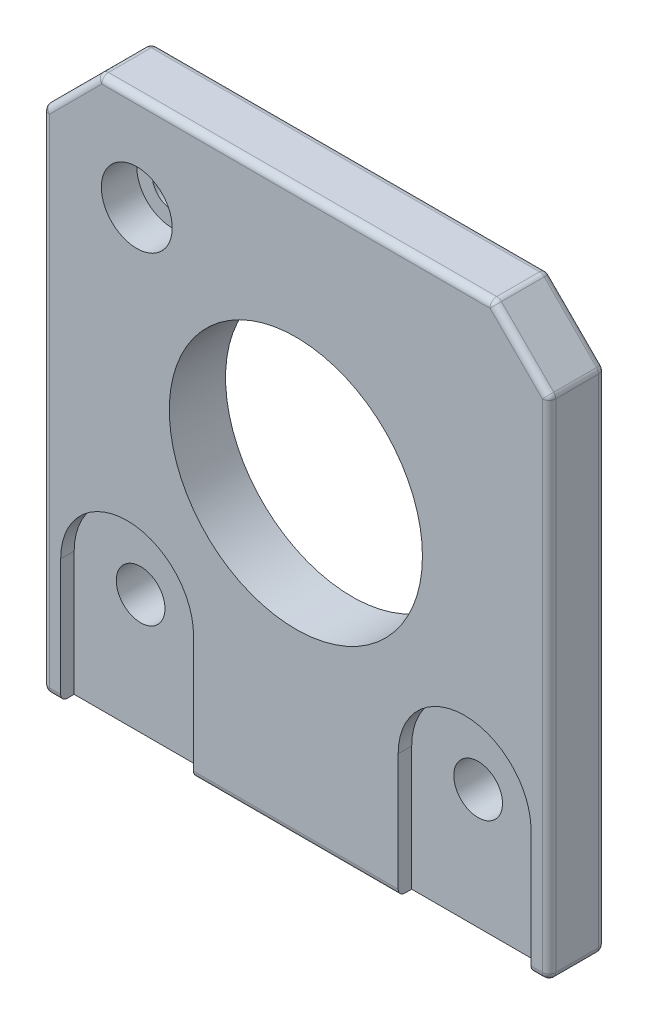
SolidWorks part; units mm, degrees
ref_plane "Front Plane" through (0, 0, 0) normal (0, 0, 1) x (1, 0, 0)
ref_plane "Top Plane" through (0, 0, 0) normal (0, 1, 0) x (1, 0, 0)
ref_plane "Right Plane" through (0, 0, 0) normal (1, 0, 0) x (0, 0, -1)
sketch "Sketch2" plane through (0, 0, 0) normal (0, 1, 0) x (1, 0, 0)
  line L1 (-28.575, 3.175) -> (28.575, 3.175)
  line L2 (-28.575, 3.175) -> (-28.575, -3.175)
  line L3 (-28.575, -3.175) -> (28.575, -3.175)
  line L4 (28.575, 3.175) -> (28.575, -3.175)
  point P4 (0, 3.175)
  point P7 (-28.575, 0)
  dimension "D1" = 6.35
  dimension "D2" = 57.15
extrude "Boss-Extrude1" add sketch "Sketch2" against normal blind 63.5
sketch "Sketch3" plane through (0, 0, 3.175) normal (0, 0, 1) x (1, 0, 0)
  line L2 (-28.575, 0) -> (28.575, 0) construction
  circle A0 centre (0, -28.815) radius 14.2875
  point P2 (0, 0)
  dimension "D1" = 28.815
  dimension "D3" = 28.575
extrude "Cut-Extrude1" cut sketch "Sketch3" against normal through all
chamfer "Chamfer1" distance 6.35 angle 45 2 edges at (-28.575, 0, 0) (28.575, 0, 0)
hole_wizard "M5 Clearance Hole1" positions "Sketch6" profile "Sketch7" hole size "M5" standard "ANSI Metric" end condition through all
sketch "Sketch6" plane through (0, 0, 3.175) normal (0, 0, 1) x (1, 0, 0)
  line L0 (-28.575, -63.5) -> (28.575, -63.5) construction
  line L1 (28.575, -63.5) -> (28.575, -6.35) construction
  point P0 (-19.05, -50)
  point P3 (19.05, -50)
  dimension "D1" = 13.5
  dimension "D2" = 9.525
  dimension "D3" = 38.1
sketch "Sketch7" plane through (-19.05, -50, 3.175) normal (1, 0, 0) x (0, -1, 0)
  line L0 (0, 0) -> (0, 6.35)
  line L1 (0, 6.35) -> (2.75, 6.35)
  line L2 (2.75, 6.35) -> (2.75, 0)
  line L5 (2.75, 0) -> (0, 0)
  line L11 (0, -6.35) -> (0, 107.95) construction
  dimension "Thru Hole Dia." = 5.5
  dimension "Thru Hole Depth" = 6.35
fillet "Fillet1" radius 0.762 18 edges at (0, -63.5, 3.175) (0, -63.5, -3.175) (28.575, -63.5, 0) (28.575, -34.925, 3.175) (28.575, -34.925, -3.175) (-28.575, -63.5, 0) (-28.575, -34.925, -3.175) (-28.575, -34.925, 3.175) (-25.4, -3.175, 3.175) (-28.575, -6.35, 0) (-25.4, -3.175, -3.175) (0, 0, 3.175) (-22.225, 0, 0) (0, 0, -3.175) (22.225, 0, 0) (25.4, -3.175, -3.175) (28.575, -6.35, 0) (25.4, -3.175, 3.175)
sketch "Sketch8" plane through (0, 0, 3.175) normal (0, 0, 1) x (1, 0, 0)
  line L0 (11.55, -63.5) -> (11.55, -49.5)
  line L1 (26.55, -49.5) -> (26.55, -63.5)
  line L2 (11.55, -63.5) -> (26.55, -63.5)
  arc A0 (11.55, -49.5) -> (26.55, -49.5) centre (19.05, -49.5) cw
  point P7 (0, 0)
extrude "Cut-Extrude4" cut sketch "Sketch8" against normal blind 1.524
mirror "Mirror1" about plane through (0, 0, 0) normal (1, 0, 0) of "Cut-Extrude4"
hole_wizard "CBORE for M4 SHCS2" positions "Sketch9" profile "Sketch10" counterbore size "M4" standard "ANSI Metric" end condition through all
sketch "Sketch9" plane through (0, 0, 3.175) normal (0, 0, 1) x (1, 0, 0)
  line L0 (-21.9094, 0) -> (21.9094, 0) construction
  point P0 (-17.9605, -10.8545)
  point P8 (0, 0)
  dimension "D1" = 10.8545
  dimension "D2" = 17.9605
sketch "Sketch10" plane through (-17.9605, -10.8545, 3.175) normal (1, 0, 0) x (0, -1, 0)
  line L0 (0, 0) -> (0, 6.35)
  line L1 (0, 6.35) -> (2.25, 6.35)
  line L3 (2.25, 6.35) -> (2.25, 4)
  line L4 (2.25, 4) -> (4, 4)
  line L5 (4, 4) -> (4, 0)
  line L7 (4, 0) -> (0, 0)
  line L11 (0, -6.35) -> (0, 107.95) construction
  dimension "Thru Hole Dia." = 4.5
  dimension "Thru Hole Depth" = 6.35
  dimension "C'Bore Dia." = 8
  dimension "C'Bore Depth" = 4
